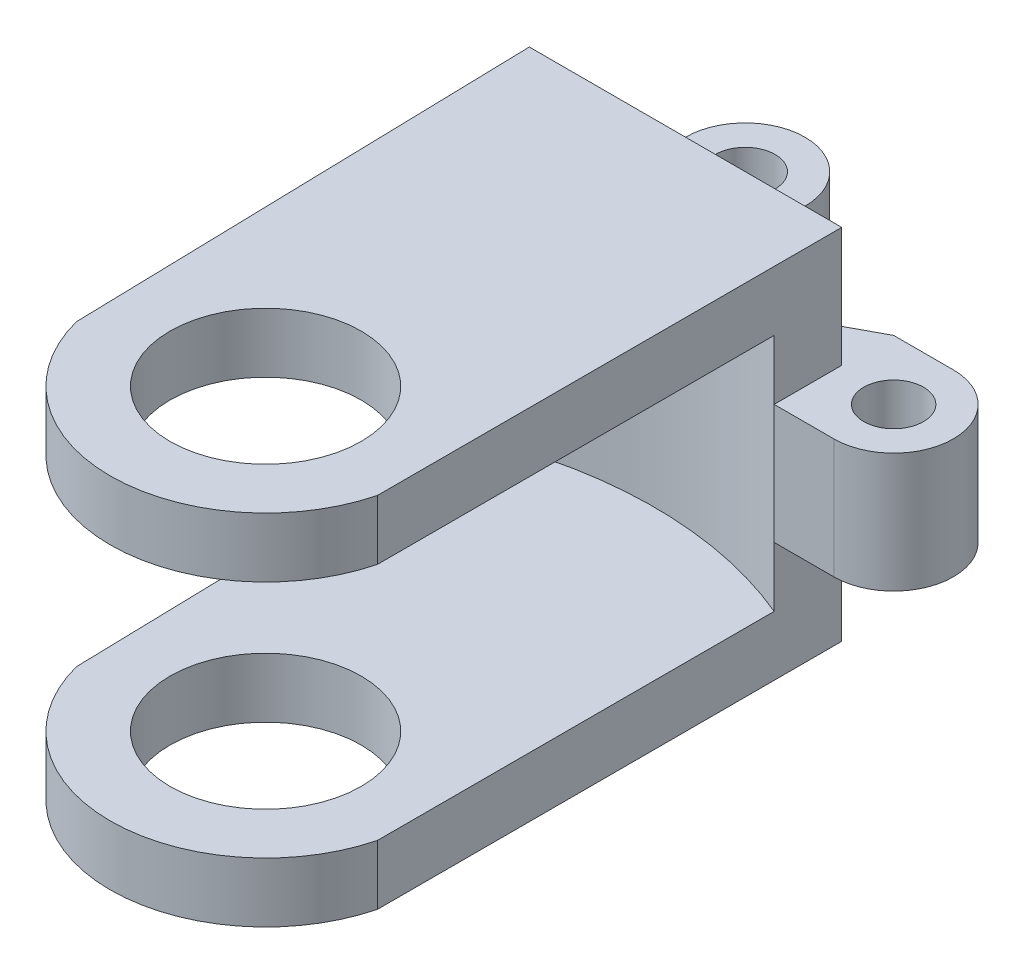
SolidWorks part; units mm, degrees
material "Plain Carbon Steel"
ref_plane "Front" through (0, 0, 0) normal (0, 0, 1) x (1, 0, 0)
ref_plane "Top" through (0, 0, 0) normal (0, 1, 0) x (1, 0, 0)
ref_plane "Right" through (0, 0, 0) normal (1, 0, 0) x (0, 0, -1)
sketch "Sketch1" plane through (0, 0, 0) normal (0, 1, 0) x (1, 0, 0)
  line L0 (-25.4, 32.5341) -> (-15.9912, -4.1063)
  line L1 (-25.4, 32.5341) -> (25.4, 32.5341)
  line L2 (-25.4, 32.5341) -> (-25.4, 45.2341)
  line L3 (-25.4, 45.2341) -> (25.4, 45.2341)
  line L4 (25.4, 32.5341) -> (25.4, 45.2341)
  line L5 (25.4, 32.5341) -> (15.9912, -4.1063)
  circle A0 centre (0, 0) radius 10.16
  circle A1 centre (0, 0) radius 16.51
  circle A2 centre (0, 0) radius 41.275
  dimension "D1" = 20.32
  dimension "D2" = 6.35
  dimension "D3" = 82.55
  dimension "D4" = 50.8
  dimension "D5" = 12.7
extrude "Boss-Extrude1" add sketch "Sketch1" along normal blind 38.1 contours A2 L4 L3 L2 | L1 A2 | A1 L5 L1 L0 | A1 A0 region at (0, 0, -21.9396) region at (0, 0, -36.0643) region at (0, 0, -41.38) region at (-2.011, 0, -15.9165)
extrude "Cut-Extrude1" cut sketch "Sketch1<3>" along normal blind 25.4 from offset 6.35 contours A1 L5 L1 L0 | L1 A2 | A1 A0 region at (0, 0, -21.9396) region at (0, 0, -36.0643) region at (-2.011, 0, -15.9165)
sketch "Sketch1<3>" plane through (0, 0, 0) normal (0, 1, 0) x (1, 0, 0) same geometry as "Sketch1"
sketch "Sketch5" plane through (0, 38.1, 0) normal (0, 1, 0) x (1, 0, 0)
  line L0 (15.9912, -4.1063) -> (15.9912, 45.2341)
  line L1 (-25.4, 45.2341) -> (25.4, 45.2341) construction
  line L2 (-15.9912, -4.1063) -> (-17.2094, 45.2341)
  line L3 (-17.2094, 45.2341) -> (-37.2976, 45.2341)
  line L4 (-37.2976, 45.2341) -> (-37.2976, -4.1063)
  line L5 (-37.2976, -4.1063) -> (40.4446, -4.1063)
  line L6 (40.4446, -4.1063) -> (40.4446, 45.2341)
  line L7 (40.4446, 45.2341) -> (15.9912, 45.2341)
  line M5 (-25.4, 45.2341) -> (-25.4, 32.5341)
  line M6 (-25.4, 32.5341) -> (-15.9912, -4.1063)
  line M8 (15.9912, -4.1063) -> (25.4, 32.5341)
  line M9 (25.4, 32.5341) -> (25.4, 45.2341)
  line M10 (25.4, 45.2341) -> (-25.4, 45.2341)
  line M15 (25.4, 45.2341) -> (-25.4, 45.2341)
extrude "Cut-Extrude2" cut sketch "Sketch5" against normal up to surface (38.1 mm away) contours L0 M8 M9 M10 | L2 M6 M15 M5 region at (19.7695, 38.1, -27.9207) region at (-20.1566, 38.1, -27.8212) up to face at (0, 0, -22.4867)
ref_plane "Plane5" through (0, 19.05, 0) normal (0, 1, 0) x (1, 0, 0)
sketch "Sketch7" plane through (0, 19.05, 0) normal (0, 1, 0) x (1, 0, 0)
  line L0 (-0.6091, 45.2341) -> (-0.6091, 51.5841)
  line L1 (-17.2094, 45.2341) -> (15.9912, 45.2341) construction
  line L2 (-6.9591, 51.5841) -> (-6.9591, 45.2341)
  line L3 (-6.9591, 45.2341) -> (5.7409, 45.2341)
  line L4 (5.7409, 45.2341) -> (5.7409, 51.5841)
  circle A0 centre (-0.6091, 51.5841) radius 6.35
  circle A1 centre (-0.6091, 51.5841) radius 3.175
  dimension "D2" = 6.35
  dimension "D1" = 6.35
extrude "Boss-Extrude2" add sketch "Sketch7" along normal blind 6.35 from offset 6.35 contours A1 A0 | A0 L2 L3 | A0 L3 L4 region at (4.3225, 19.05, -46.6525) region at (-5.5407, 19.05, -46.6525) region at (-4.9722, 19.05, -47.2209)
sketch "Sketch8" plane through (0, 19.05, 0) normal (0, 1, 0) x (1, 0, 0)
  line L0 (15.9912, 38.0514) -> (22.3412, 38.0514)
  line L1 (15.9912, -4.1063) -> (15.9912, 45.2341) construction
  line L2 (15.9912, 38.0514) -> (15.9912, 50.7514)
  line L3 (15.9912, 50.7514) -> (22.3412, 50.7514)
  line L4 (22.3412, 50.7514) -> (22.3412, 38.0514)
  line L5 (5.7409, 45.2341) -> (15.9912, 50.7514)
  line L6 (15.9912, 50.7514) -> (15.9912, 45.2341)
  line L7 (15.9912, 45.2341) -> (5.7409, 45.2341)
  circle A0 centre (22.3412, 44.4014) radius 6.35
  circle A1 centre (22.3412, 44.4014) radius 3.175
  dimension "D3" = 6.35
  dimension "D1" = 6.35
  dimension "D2" = 12.7
extrude "Boss-Extrude3" add sketch "Sketch8" along normal blind 6.35 contours A1 L4 A0 | A1 L4 A0 | A0 L3 L2 | A0 L2 L0 | L6 L7 L5 region at (17.4096, 19.05, -39.4698) region at (17.9515, 19.05, -40.0117) region at (22.4832, 19.05, -39.6389) region at (17.4096, 19.05, -49.333)
mirror "Mirror1" about plane through (0, 19.05, 0) normal (0, 1, 0) of "Boss-Extrude2", "Boss-Extrude3"
